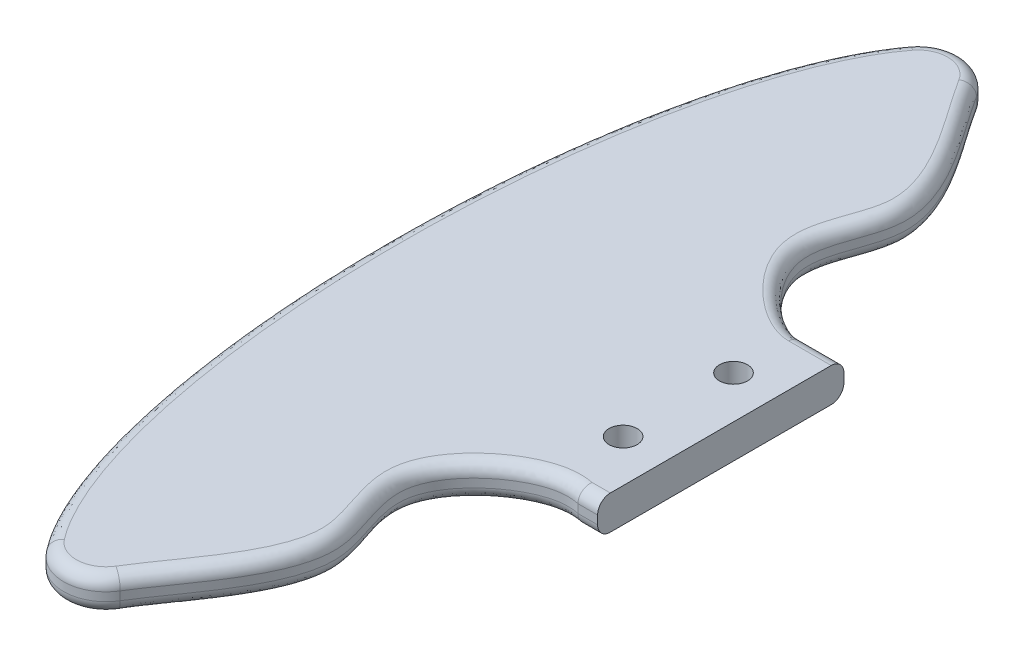
SolidWorks part; units mm, degrees
ref_plane "Ebene vorne" through (0, 0, 0) normal (0, 0, 1) x (1, 0, 0)
ref_plane "Ebene oben" through (0, 0, 0) normal (0, 1, 0) x (1, 0, 0)
ref_plane "Ebene rechts" through (0, 0, 0) normal (1, 0, 0) x (0, 0, -1)
sketch "Sketch1" plane through (0, 0, 0) normal (0, 1, 0) x (1, 0, 0)
  line L0 (19.5662, 0) -> (21.8809, 0) construction
  line L1 (16.8809, -14.5) -> (21.8809, -14.5)
  line L3 (16.8809, 14.5) -> (21.8809, 14.5)
  line L4 (21.8809, -14.5) -> (21.8809, 14.5)
  line L5 (17.5, 0) -> (9.7386, 0) construction
  ellipse E0 centre (0, 0) end of major axis (0, -55) minor radius 17.5 (16.8809, 14.5) -> (16.8809, -14.5) ccw
  dimension "D1" = 110
  dimension "D2" = 35
  dimension "D3" = 29
  dimension "D4" = 5
extrude "Boss-Extrude1" add sketch "Sketch1" along normal blind 4
sketch "Sketch2" plane through (0, 4, 0) normal (0, 1, 0) x (1, 0, 0)
  line L0 (16.8809, -14.5) -> (21.8809, -14.5) construction
  line L1 (21.8809, 14.5) -> (7.8809, 14.5)
  line L2 (21.8809, 14.5) -> (21.8809, -14.5)
  line L3 (21.8809, -14.5) -> (7.8809, -14.5)
  line L4 (7.8809, 14.5) -> (7.8809, -14.5)
  dimension "D1" = 14
extrude "Spacer" [suppressed] add sketch "Sketch2" along normal blind 5
sketch "Sketch4" [suppressed] plane through (0, 0, -14.5) normal (0, 0, -1) x (-1, 0, 0)
  line L0 (-25.2924, 9) -> (-39.2924, 3.9044)
  line L2 (-39.2924, 3.9044) -> (-39.2924, 9)
  line L3 (-39.2924, 9) -> (-25.2924, 9)
  dimension "D1" = 70
extrude "Angle" [suppressed] cut sketch "Sketch4" against normal up to surface (29 mm away) up to face at (19.3809, 2, 14.5)
sketch "Sketch6" [suppressed] plane through (5.8512, 16.076, 0) normal (0.342, 0.9397, 0) x (0.9397, -0.342, 0)
  line L0 (28.0874, 6.5) -> (28.0874, -6.5) construction
  line L1 (35.5874, -14.5) -> (35.5874, 14.5) construction
  line L2 (35.5874, 0) -> (20.6889, 0) construction
  line L3 (20.6889, 14.5) -> (20.6889, -14.5) construction
  line L4 (28.0874, 0) -> (51.5252, 0) construction
  circle A0 centre (28.0874, 6.5) radius 1.65
  circle A1 centre (28.0874, -6.5) radius 1.65
  dimension "D1" = 3.3
  dimension "D2" = 13
  dimension "D3" = 7.5
extrude "Cut-Extrude1" [suppressed] cut sketch "Sketch6" against normal through all
sketch "Sketch7" plane through (0, 4, 0) normal (0, 1, 0) x (1, 0, 0)
  line L0 (0, 55) -> (0, 12.0004) construction
  line L1 (-17.5, 0) -> (-3.5208, 0) construction
  line L2 (21.8809, 14.5) -> (16.8809, 14.5) construction
  line L3 (0, -55) -> (0, -15.7144) construction
  line L4 (16.8809, -14.5) -> (21.8809, -14.5) construction
  ellipse E0 centre (0, 0) end of major axis (0, -55) minor radius 17.5 (16.8809, 14.5) -> (16.8809, -14.5) ccw construction
  spline S0 degree 3 poles (62.2162, 43.7631) (14.9727, 40.778) (23.6962, 6.6255) (4.3063, 22.6804) (15.579, 37.0989) (-21.5373, 68.377) (62.2162, 43.7631) (14.9727, 40.778) (23.6962, 6.6255) knots -0.653805 -0.468518 -0.148074 0 0.169799 0.265053 0.346195 0.531482 0.851926 1 1.169799 1.265053 1.346195 only from (23.1423, 35.5) to (23.1423, 35.5)
  spline S1 degree 3 poles (29.5593, -31.5853) (23.5482, -6.7086) (4.6782, -22.3634) (15.3041, -37.4017) (-20.7557, -66.7321) (50.8787, -53.0229) (29.5593, -31.5853) (23.5482, -6.7086) (4.6782, -22.3634) knots -0.629537 -0.301314 -0.217767 0 0.097566 0.180678 0.370463 0.698686 0.782233 1 1.097566 1.180678 1.370463 only from (16.8809, -14.5) to (16.8809, -14.5)
  dimension "D3" = 20
  dimension "D1" = 10
  dimension "D2" = 8
  dimension "D4" = 40
  dimension "D5" = 21
  dimension "D6" = 30
  dimension "D7" = 21
  dimension "D8" = 32
  dimension "D9" = 40
  dimension "D10" = 30
  dimension "D11" = 32
  dimension "D12" = 10
  dimension "D13" = 8
  dimension "D14" = 20
extrude "Cut-Extrude3" cut sketch "Sketch7" against normal blind 10
fillet "Fillet1" radius 5 1 edges at (0, 2, -55) type face fillet first side face at (-8.75, 2, 0) second side face at (4.2202, 2, -44.875)
fillet "Fillet2" radius 5 1 edges at (0, 2, 55) type face fillet first side face at (-10.249, 2, 6.3702) second side face at (14.672, 2, 24.625)
fillet "Fillet4" radius 1.5 6 edges at (-2.4904, 4, 52.7328) (-2.4565, 4, -52.7957) (-17.5, 4, -0.1095) (20.7218, 4, 14.5) type face fillet first side face at (7.5793, 4, -4.5155) second side face at (5.3714, 2, -41.4637) second side face at (-2.5098, 2, -51.7257) second side face at (-12.0967, 2, -0.0757) second side face at (-2.5476, 2, 51.6461) second side face at (15.051, 2, 23.4606) second side face at (20.7218, 2, 14.5)
fillet "Fillet5" radius 1.5 6 edges at (-2.4904, 0, 52.7328) (-2.4565, 0, -52.7957) (-17.5, 0, -0.1095) (20.7218, 0, 14.5) type face fillet first side face at (7.5793, 0, -4.5155) second side face at (7.1335, 1.25, -35.8234) second side face at (-2.5098, 1.25, -51.7257) second side face at (-11.0552, 1.25, 8.8565) second side face at (-2.5476, 1.25, 51.6461) second side face at (12.153, 1.25, 25.6389) second side face at (20.7218, 1.25, 14.5)
sketch "Sketch8" plane through (0, 4, 0) normal (0, 1, 0) x (1, 0, 0)
  line L0 (21.8809, 0) -> (10.7021, 0) construction
  line L1 (21.8809, -13) -> (21.8809, 13) construction
  line L2 (16.8809, -6.5) -> (16.8809, 6.5) construction
  line L3 (16.8809, 0) -> (25.6639, 0) construction
  circle A0 centre (16.8809, -6.5) radius 1.65
  circle A1 centre (16.8809, 6.5) radius 1.65
  dimension "D1" = 3.3
  dimension "D2" = 5
  dimension "D3" = 13
extrude "M3 Screws no Angle" cut sketch "Sketch8" against normal through all
